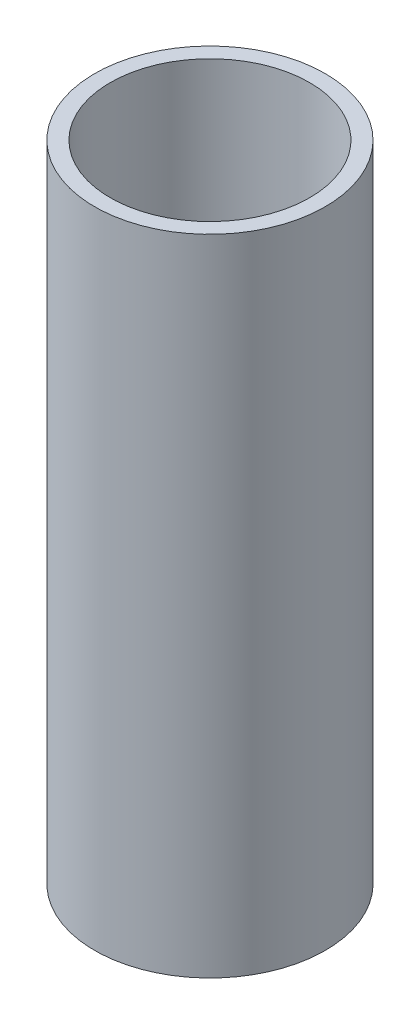
SolidWorks part; units mm, degrees
ref_plane "Front Plane" through (0, 0, 0) normal (0, 0, 1) x (1, 0, 0)
ref_plane "Top Plane" through (0, 0, 0) normal (0, 1, 0) x (1, 0, 0)
ref_plane "Right Plane" through (0, 0, 0) normal (1, 0, 0) x (0, 0, -1)
sketch "Sketch1" plane through (0, 0, 0) normal (0, 1, 0) x (1, 0, 0)
  circle A0 centre (0, 0) radius 42.5
  dimension "SLEEVE_OD" = 85
extrude "Boss-Extrude1" add sketch "Sketch1" along normal blind 237.3492
sketch "Sketch2" plane through (0, 0, 0) normal (0, 1, 0) x (1, 0, 0)
  circle A0 centre (0, 0) radius 36.756
  dimension "BORE_D" = 73.512
extrude "Cut-Extrude1" cut sketch "Sketch2" along normal through all
chamfer "Chamfer1" distance 3.9315 angle 60 rebuild error yes
